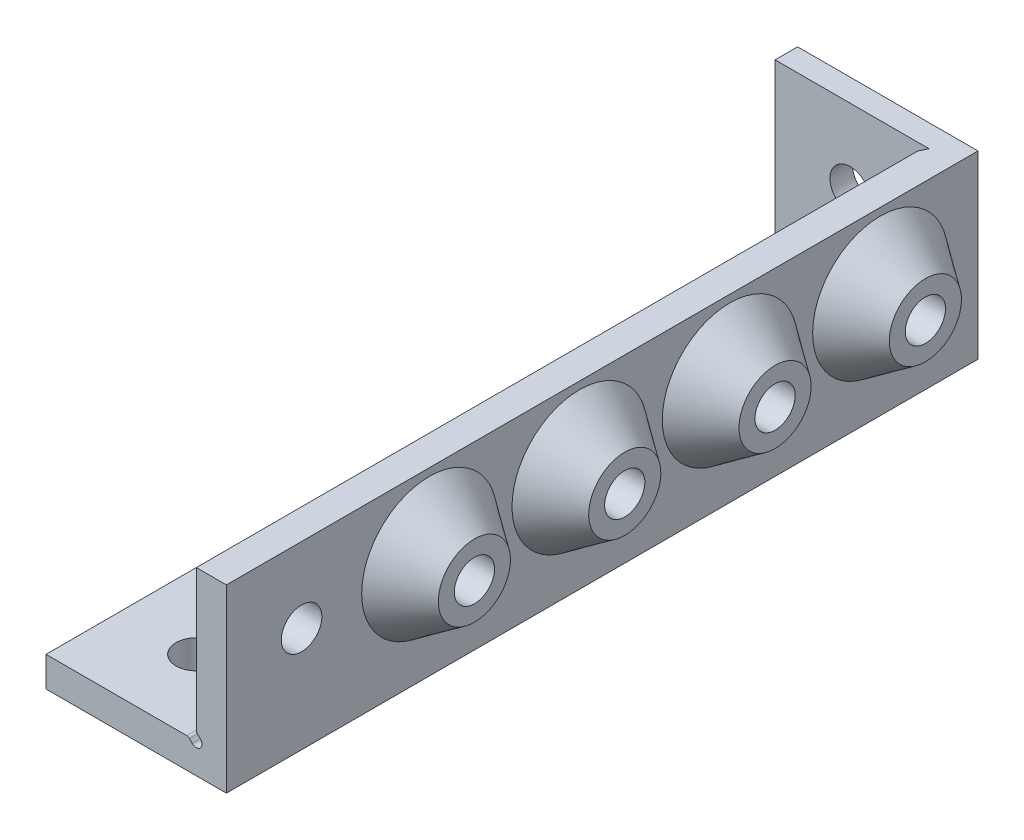
SolidWorks part; units mm, degrees
ref_plane "Front Plane" through (0, 0, 0) normal (0, 0, 1) x (1, 0, 0)
ref_plane "Top Plane" through (0, 0, 0) normal (0, 1, 0) x (1, 0, 0)
ref_plane "Right Plane" through (0, 0, 0) normal (1, 0, 0) x (0, 0, -1)
sketch "Sketch1" plane through (0, 0, 0) normal (0, 0, 1) x (1, 0, 0)
  line L0 (-20, 0) -> (-20, -4)
  line L1 (-1.2678, 0) -> (-20, 0)
  line L2 (0, 1.2678) -> (0, 20)
  line L3 (0, 20) -> (-20, 20)
  line L4 (-20, 0) -> (-20, 20)
  line L5 (-20, -4) -> (4, -4)
  line L6 (4, -4) -> (4, 20)
  line L7 (4, 20) -> (0, 20)
  line L8 (0.5303, 0.5303) -> (0.1464, 0.9142)
  line L9 (-0.5303, -0.5303) -> (-0.9142, -0.1464)
  line L10 (-10, 20) -> (-10, 0) construction
  line L11 (-20, 10) -> (0, 10) construction
  arc A0 (-0.5303, -0.5303) -> (0.5303, 0.5303) centre (0, 0) ccw
  arc A1 (0, 1.2678) -> (0.1464, 0.9142) centre (0.5, 1.2678) ccw
  arc A2 (-1.2678, 0) -> (-0.9142, -0.1464) centre (-1.2678, -0.5) cw
  circle A3 centre (-10, 10) radius 2.7
  dimension "D5" = 1.5
  dimension "D8" = 0.5
  dimension "D9" = 5.4
  dimension "D1" = 20
  dimension "D2" = 20
  dimension "D3" = 4
  dimension "D4" = 4
  dimension "D6" = 135
  dimension "D7" = 135
extrude "Boss-Extrude1" add sketch "Sketch1" along normal blind 3 contours L1 A2 L9 A0 L8 A1 L2 L3 L4 region at (-19.7066, 10, 0)
extrude "Boss-Extrude2" add sketch "Sketch1<4>" along normal blind 100 contours A2 L1 L0 L5 L6 L7 L2 A1 L8 A0 L9 region at (-10.6339, -0.3394, 0)
sketch "Sketch1<4>" plane through (0, 0, 0) normal (0, 0, 1) x (1, 0, 0) same geometry as "Sketch1"
sketch "Sketch2" plane through (0, 20, 0) normal (0, 1, 0) x (1, 0, 0)
  line L0 (0, -3) -> (0.5, -3)
  line L1 (0.5, -3) -> (0, -4)
  line L2 (0, -100) -> (0, -3) construction
  line L3 (0, -4) -> (0, -3)
  dimension "D1" = 1
  dimension "D2" = 0.5
extrude "Cut-Extrude1" cut sketch "Sketch2" against normal blind 20
sketch "Sketch3" plane through (-20, 0, 0) normal (-1, 0, 0) x (0, 0, 1)
  line L0 (3, 0) -> (3, -0.5)
  line L1 (3, -0.5) -> (4, 0)
  line L2 (100, 0) -> (3, 0) construction
  line L3 (4, 0) -> (3, 0)
  dimension "D1" = 0.5
  dimension "D2" = 1
extrude "Cut-Extrude2" cut sketch "Sketch3" against normal blind 20
sketch "Sketch4" plane through (4, 0, 0) normal (1, 0, 0) x (0, 0, -1)
  line L0 (0, 10) -> (-100, 10) construction
  line L1 (0, -4) -> (0, 20) construction
  line L2 (-100, -4) -> (-100, 20) construction
  line L3 (-100, 20) -> (0, 20) construction
  line L4 (-3, 0.5607) -> (-3, 20) construction
  circle A0 centre (-13, 10) radius 2.675
  circle A1 centre (-33, 10) radius 2.675
  circle A2 centre (-53, 10) radius 2.675
  circle A3 centre (-73, 10) radius 2.675
  circle A4 centre (-13, 10) radius 9
  circle A5 centre (-33, 10) radius 9
  circle A6 centre (-53, 10) radius 9
  circle A7 centre (-73, 10) radius 9
  circle A8 centre (-90, 10) radius 2.7
  dimension "D2" = 10
  dimension "D3" = 5.35
  dimension "D5" = 18
  dimension "D6" = 10
  dimension "D7" = 5.4
  dimension "D1" = 10
  dimension "D4" = 4
extrude "Boss-Extrude3" add sketch "Sketch4" along normal blind 6 draft 35 contours A4 L0 A0 | L0 A4 A0 | L0 A0 | A0 L0 | L0 A5 A1 | A5 L0 A1 | L0 A1 | A1 L0 | L0 A6 A2 | A6 L0 A2 | L0 A2 | A2 L0 | L0 A7 A3 | A7 L0 A3 | L0 A3 | A3 L0 region at (4, 5.9202, 13) region at (4, 14.0798, 13) region at (4, 5.9202, 73) region at (4, 14.0798, 73) region at (4, 5.9202, 53) region at (4, 14.0798, 53) region at (4, 5.9202, 33) region at (4, 14.0798, 33) region at (4, 8.8647, 13) region at (4, 11.1353, 13) region at (4, 8.8647, 33) region at (4, 11.1353, 33) region at (4, 8.8647, 53) region at (4, 11.1353, 53) region at (4, 8.8647, 73) region at (4, 11.1353, 73)
extrude "Cut-Extrude3" cut sketch "Sketch4<3>" against normal up to surface and the other way up to surface contours A0 | A1 | A2 | A3 | A8 up to face at (0, 10.6339, 52) other way up to face at (10, 14.7988, 73)
sketch "Sketch4<3>" plane through (4, 0, 0) normal (1, 0, 0) x (0, 0, -1) same geometry as "Sketch4"
ref_plane "Plane1" through (-8, 8, 0) normal (-0.7071, 0.7071, 0) x (0.7071, 0.7071, 0)
ref_plane "Plane2" through (0, 0, 0) normal (0.7071, 0.7071, 0) x (0, 0, -1)
mirror "Mirror1" about plane through (0, 0, 0) normal (0.7071, 0.7071, 0) of "Boss-Extrude3"
sketch "Sketch5" plane through (0, -10, 0) normal (0, -1, 0) x (1, 0, 0)
  line L0 (-10, 13) -> (-10, 100) construction
  line L1 (-20, 100) -> (4, 100) construction
  circle A0 centre (-10, 13) radius 2.675
  circle A1 centre (-10, 90) radius 2.7
  circle A2 centre (-10, 33) radius 2.675
  circle A3 centre (-10, 53) radius 2.675
  circle A4 centre (-10, 73) radius 2.675
  dimension "D1" = 10
  dimension "D2" = 5.4
  dimension "D3" = 5.35
  dimension "D4" = 4
extrude "Cut-Extrude4" cut sketch "Sketch5" against normal up to surface (10 mm away) up to face at (-10.6339, 0, 52)
